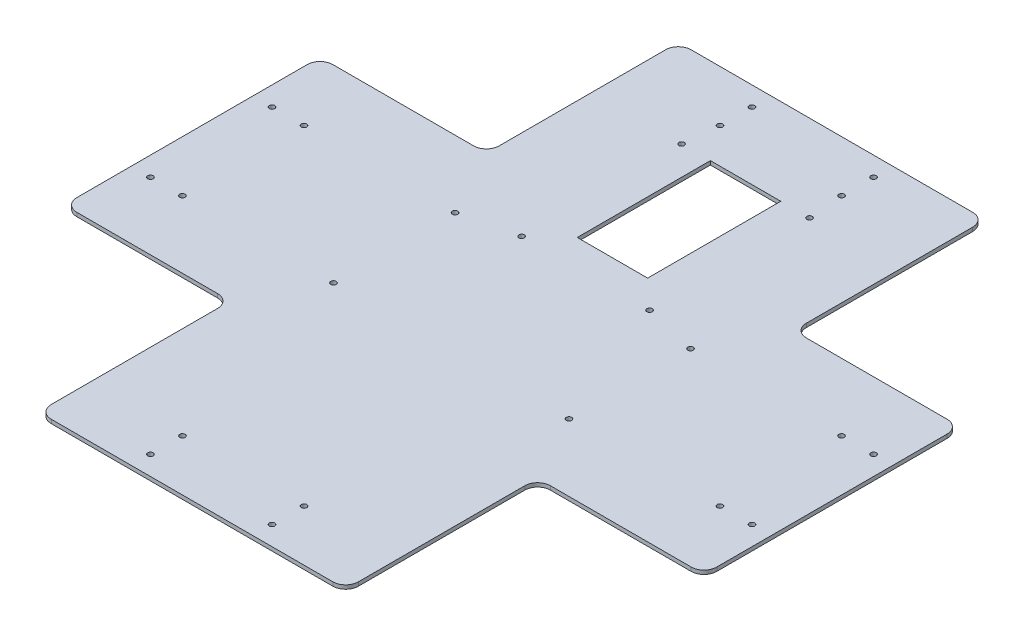
SolidWorks part; units mm, degrees
ref_plane "Front Plane" through (0, 0, 0) normal (0, 0, 1) x (1, 0, 0)
ref_plane "Top Plane" through (0, 0, 0) normal (0, 1, 0) x (1, 0, 0)
ref_plane "Right Plane" through (0, 0, 0) normal (1, 0, 0) x (0, 0, -1)
sketch "Sketch1" plane through (0, 0, 0) normal (0, 1, 0) x (1, 0, 0)
  line L0 (120, 250) -> (-120, 250)
  line L1 (-120, 250) -> (-120, 100)
  line L2 (-120, 100) -> (-250, 100)
  line L3 (-250, 100) -> (-250, -100)
  line L4 (0, 319.0603) -> (0, -214.0477) construction
  line L5 (-295.2994, 0) -> (181.6639, 0) construction
  line L6 (250, 100) -> (250, -100)
  line L7 (120, 100) -> (250, 100)
  line L8 (120, 250) -> (120, 100)
  line L9 (120, -250) -> (120, -100)
  line L10 (120, -100) -> (250, -100)
  line L11 (-120, -100) -> (-250, -100)
  line L12 (-120, -250) -> (-120, -100)
  line L13 (120, -250) -> (-120, -250)
  point P14 (0, 250)
  point P15 (-250, 0)
  point P16 (250, 0)
  point P20 (0, -250)
  dimension "D1" = 120
  dimension "D2" = 150
  dimension "150" = 130
  dimension "D3" = 100
extrude "Base" add sketch "Sketch1" along normal blind 3
fillet "Fillet1" radius 10 12 edges at (120, 1.5, -100) (250, 1.5, -100) (250, 1.5, 100) (120, 1.5, 100) (120, 1.5, 250) (-120, 1.5, 250) (-120, 1.5, 100) (-250, 1.5, 100) (-250, 1.5, -100) (-120, 1.5, -100) (-120, 1.5, -250) (120, 1.5, -250)
sketch "Sketch2" plane through (0, 3, 0) normal (0, 1, 0) x (1, 0, 0)
  line L0 (0, 268.1887) -> (0, -286.5172) construction
  line L1 (-278.1616, 0) -> (318.0529, 0) construction
  line L2 (110, 250) -> (-110, 250) construction
  line L3 (-250, 90) -> (-250, -90) construction
  circle A0 centre (-47.5, 235) radius 2.125
  circle A1 centre (-47.5, 210) radius 2.125
  circle A2 centre (-235, 47.5) radius 2.125
  circle A3 centre (-210, 47.5) radius 2.125
  circle A4 centre (-210, -47.5) radius 2.125
  circle A5 centre (-235, -47.5) radius 2.125
  circle A6 centre (235, -47.5) radius 2.125
  circle A7 centre (210, -47.5) radius 2.125
  circle A8 centre (210, 47.5) radius 2.125
  circle A9 centre (235, 47.5) radius 2.125
  circle A10 centre (47.5, 210) radius 2.125
  circle A11 centre (47.5, 235) radius 2.125
  circle A12 centre (47.5, -235) radius 2.125
  circle A13 centre (47.5, -210) radius 2.125
  circle A14 centre (-47.5, -210) radius 2.125
  circle A15 centre (-47.5, -235) radius 2.125
  dimension "D1" = 4.25
  dimension "D2" = 4.25
  dimension "D3" = 4.25
  dimension "D4" = 4.25
  dimension "D5" = 47.5
  dimension "D6" = 25
  dimension "D7" = 15
  dimension "D8" = 25
  dimension "D9" = 15
  dimension "D10" = 47.5
extrude "Armor Module Holes" cut sketch "Sketch2" against normal blind 3
sketch "Sketch3" plane through (0, 3, 0) normal (0, 1, 0) x (1, 0, 0)
  line L0 (-268.1887, 0) -> (424.969, 0) construction
  line L1 (0, 281.6655) -> (0, -321.0178) construction
  line L2 (-149.3232, 150) -> (229.1059, 150) construction
  circle A0 centre (92, 47.5) radius 2.125
  circle A1 centre (92, -47.5) radius 2.125
  circle A2 centre (-92, -47.5) radius 2.125
  circle A3 centre (-92, 47.5) radius 2.125
  dimension "D2" = 4.25
  dimension "D1" = 150
  dimension "D3" = 47.5
  dimension "D4" = 92
extrude "Plates for Gimbal" cut sketch "Sketch3" against normal blind 3
sketch "Sketch4" plane through (0, 3, 0) normal (0, 1, 0) x (1, 0, 0)
  line L0 (0, 192.0447) -> (0, -152.0634) construction
  line L1 (60, 192.0447) -> (60, -152.0634) construction
  line L2 (-60, 192.0447) -> (-60, -152.0634) construction
  line L3 (-89.875, 47.5) -> (89.875, 47.5) construction
  line L4 (-79.064, 192.5) -> (97.4823, 192.5) construction
  line L6 (-27.5, 182.5) -> (27.5, 182.5)
  line L7 (-27.5, 182.5) -> (-27.5, 78.5)
  line L8 (-27.5, 78.5) -> (27.5, 78.5)
  line L9 (27.5, 182.5) -> (27.5, 78.5)
  circle A0 centre (-92, 47.5) radius 2.125 construction
  circle A1 centre (92, 47.5) radius 2.125 construction
  circle A2 centre (-50, 182.5) radius 2.125
  circle A3 centre (50, 182.5) radius 2.125
  circle A4 centre (50, 57.5) radius 2.125
  circle A5 centre (-50, 57.5) radius 2.125
  dimension "D4" = 4.25
  dimension "D5" = 4.25
  dimension "D6" = 4.25
  dimension "D7" = 4.25
  dimension "D1" = 60
  dimension "D2" = 145
  dimension "D3" = 120
  dimension "D8" = 10
  dimension "D9" = 10
  dimension "D10" = 10
  dimension "D11" = 10
  dimension "D12" = 10
  dimension "D13" = 104
  dimension "D14" = 27.5
  dimension "D15" = 55
extrude "Battery Mount" cut sketch "Sketch4" against normal blind 10
